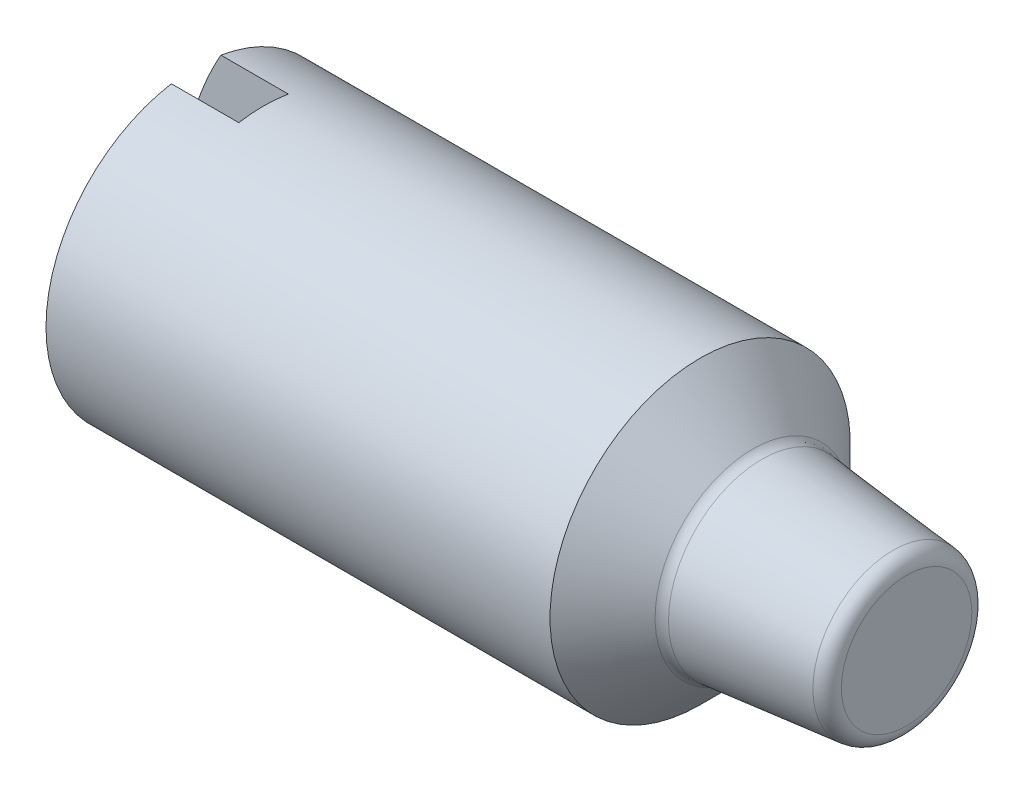
SolidWorks part; units mm, degrees
ref_plane "Front" through (0, 0, 0) normal (0, 0, 1) x (1, 0, 0)
ref_plane "Top" through (0, 0, 0) normal (0, 1, 0) x (1, 0, 0)
ref_plane "Right" through (0, 0, 0) normal (1, 0, 0) x (0, 0, -1)
sketch "Sketch1" plane through (0, 0, 0) normal (0, 0, 1) x (1, 0, 0)
  line L0 (10, 0) -> (0, 0)
  line L1 (10, 0) -> (10, 1.05)
  line L2 (10, 1.05) -> (8, 1.25)
  line L3 (8, 1.25) -> (7.25, 2)
  line L4 (7.25, 2) -> (0.5359, 2)
  line L5 (-8.5703, 0) -> (3.0325, 0) construction
  arc A0 (0.5359, 2) -> (0, 0) centre (4, 0) ccw
  dimension "D2" = 45
revolve "Base" add sketch "Sketch1" angle 360 about L5
cosmetic thread "ThreadCosmetic1" [suppressed] parameters "D2"=3
sketch "Sketch2" plane through (0, 0, 0) normal (0, 1, 0) x (1, 0, 0)
  line L1 (1.4336, 0.33) -> (0.0136, 0.33)
  line L2 (1.4336, 0.33) -> (1.4336, -0.33)
  line L3 (1.4336, -0.33) -> (0.0136, -0.33)
  arc A0 (0.5359, 2) -> (0.5359, -2) centre (4, 0) ccw construction
  arc A1 (0.0136, -0.33) -> (0.0136, 0.33) centre (0.0136, 0) cw
  dimension "m" = 0.33
extrude "Notch" cut sketch "Sketch2" against normal through all and the other way through all
fillet "Fillet" radius 0.2 2 edges at (10, -1.05, 0) (8, -1.25, 0)
sketch "Sketch3" plane through (0, 0, 0) normal (0, 0, 1) x (1, 0, 0)
  line L0 (7.25, 1.567) -> (7.5, 2)
  line L1 (7.5, 2) -> (7.5, 2.5)
  line L2 (7.5, 2.5) -> (7, 2.5)
  line L3 (7, 2.5) -> (7, 2)
  line L4 (7, 2) -> (7.25, 1.567)
  line L5 (0, 0) -> (11.147, 0) construction
  line L7 (7.25, -2) -> (7.25, 2) construction
  line L8 (7.25, 2) -> (0.5359, 2) construction
  dimension "D1" = 0.5
revolve "Cut-Revolve10" [suppressed] cut sketch "Sketch3" angle 360 about L5
pattern_linear "LPattern10" [suppressed] count 12 spacing 0.6 along (-1, 0, 0) of bodies 103
equation "\"m@Sketch2\" = \"n@Sketch2\" / 2"
equation "\"d1@Sketch1\" = \"dp@Sketch1\" - \"z@Sketch1\" / 5"
equation "\"D1@Sketch3\" = (  \"d@Sketch1\" - \"D2@ThreadCosmetic1\" )  / 2"
equation "\"D3@LPattern10\" = \"D1@Sketch3\" * 1.2"
equation "\"D1@LPattern10\" = (  \"l@Sketch1\" - \"z@Sketch1\" -  ( \"d@Sketch1\" - \"d1@Sketch1\" )  / 2 )  / \"D3@LPattern10\""
